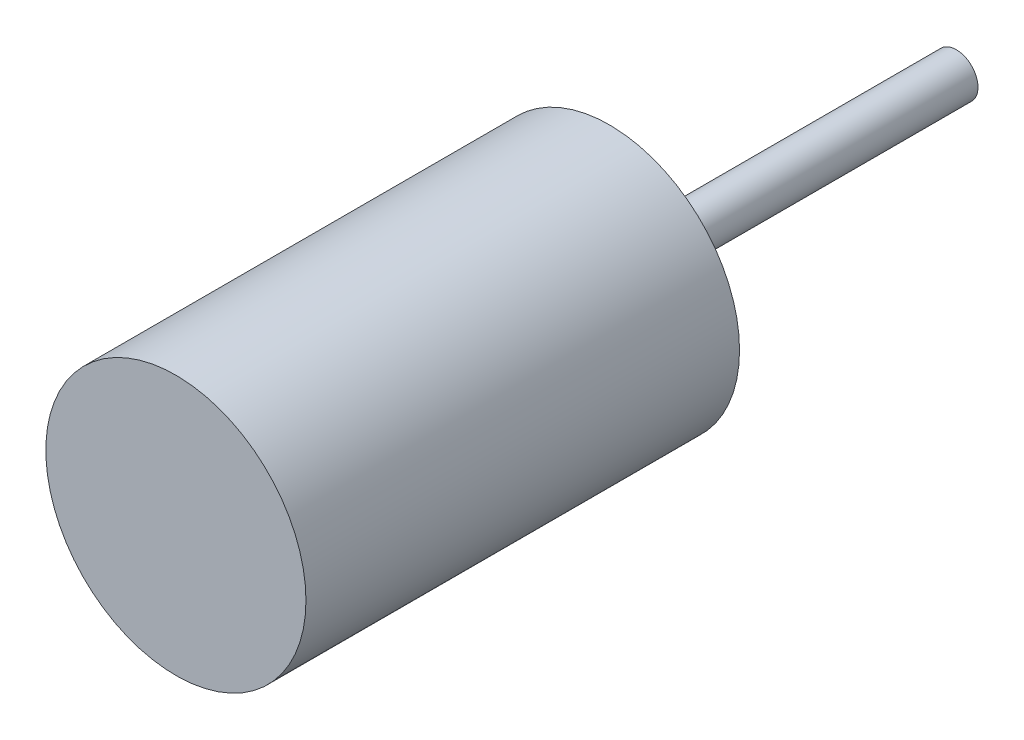
SolidWorks part; units mm, degrees
ref_plane "Front Plane" through (0, 0, 0) normal (0, 0, 1) x (1, 0, 0)
ref_plane "Top Plane" through (0, 0, 0) normal (0, 1, 0) x (1, 0, 0)
ref_plane "Right Plane" through (0, 0, 0) normal (1, 0, 0) x (0, 0, -1)
sketch "Sketch1" plane through (0, 0, 0) normal (0, 0, 1) x (1, 0, 0)
  circle A0 centre (0, 0) radius 0.5
extrude "Boss-Extrude1" add sketch "Sketch1" along normal blind 8
sketch "Sketch2" plane through (0, 0, 8) normal (0, 0, 1) x (1, 0, 0)
  circle A0 centre (0, 0) radius 3
extrude "Boss-Extrude2" add sketch "Sketch2" along normal blind 10
